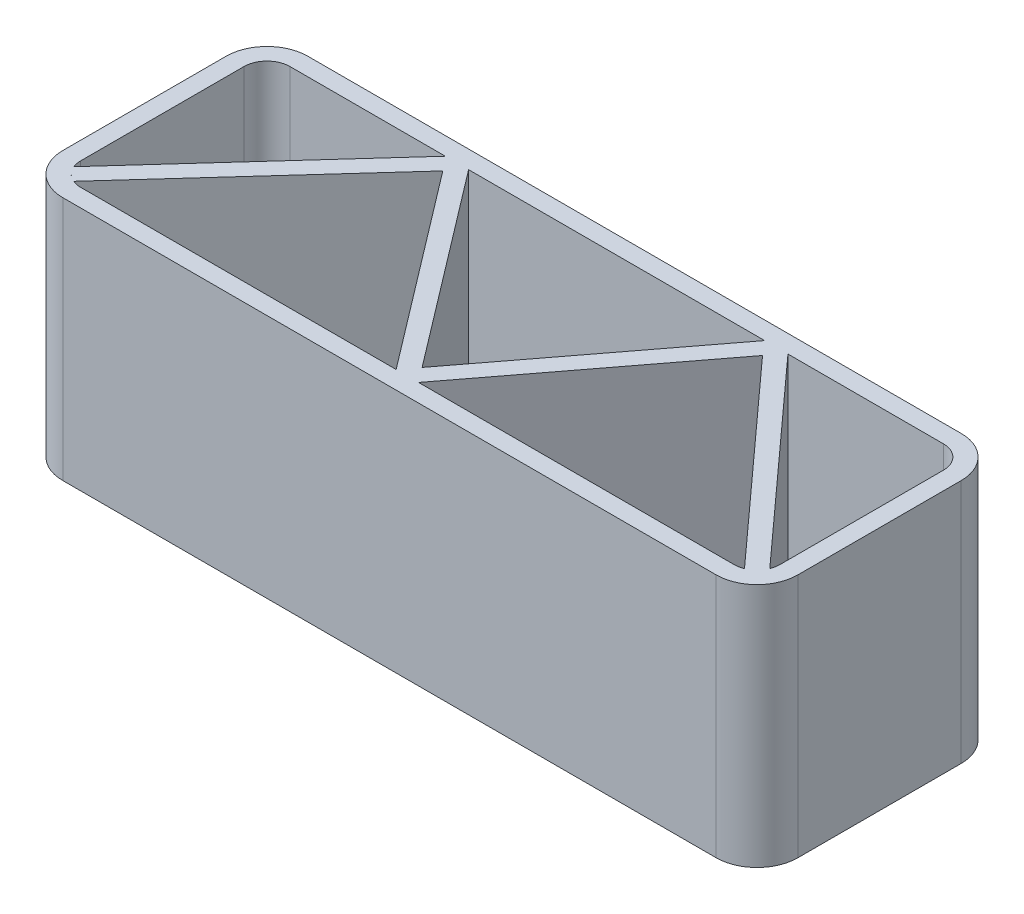
SolidWorks part; units mm, degrees
ref_plane "Front Plane" through (0, 0, 0) normal (0, 0, 1) x (1, 0, 0)
ref_plane "Top Plane" through (0, 0, 0) normal (0, 1, 0) x (1, 0, 0)
ref_plane "Right Plane" through (0, 0, 0) normal (1, 0, 0) x (0, 0, -1)
sketch "Sketch1" plane through (0, 0, 0) normal (0, 1, 0) x (1, 0, 0)
  line L1 (-406.4, 152.4) -> (406.4, 152.4)
  line L2 (-457.2, 101.6) -> (-457.2, -101.6)
  line L3 (-406.4, -152.4) -> (406.4, -152.4)
  line L4 (457.2, 101.6) -> (457.2, -101.6)
  line L5 (-457.2, 152.4) -> (457.2, -152.4) construction
  line L6 (-457.2, -152.4) -> (457.2, 152.4) construction
  arc A0 (406.4, 152.4) -> (457.2, 101.6) centre (406.4, 101.6) cw
  arc A1 (406.4, -152.4) -> (457.2, -101.6) centre (406.4, -101.6) ccw
  arc A2 (-457.2, -101.6) -> (-406.4, -152.4) centre (-406.4, -101.6) ccw
  arc A3 (-406.4, 152.4) -> (-457.2, 101.6) centre (-406.4, 101.6) ccw
  point P0 (0, 0)
  dimension "D3" = 50.8
  dimension "D1" = 914.4
  dimension "D2" = 304.8
extrude "Extrude-Thin1" add sketch "Sketch1" along normal blind 304.8 thin thin type one direction reverse wall 22.225
sketch "Sketch2" plane through (0, 304.8, 0) normal (0, 1, 0) x (1, 0, 0)
  line L0 (-426.6056, -121.8056) -> (-198.1098, 130.175)
  line L1 (406.4, 130.175) -> (-406.4, 130.175) construction
  line L3 (-198.1098, 130.175) -> (0, -130.175)
  line L4 (-406.4, -130.175) -> (406.4, -130.175) construction
  line L6 (0, -130.175) -> (198.1098, 130.175)
  line L7 (198.1098, 130.175) -> (426.6056, -121.8056)
  arc A0 (-434.975, -101.6) -> (-406.4, -130.175) centre (-406.4, -101.6) ccw construction
  arc A1 (406.4, -130.175) -> (434.975, -101.6) centre (406.4, -101.6) ccw construction
extrude "Extrude-Thin3" add sketch "Sketch2" against normal up to vertex (304.8 mm away) thin up to point (-406.4, 0, -130.175) thin type mid plane wall 22.225
